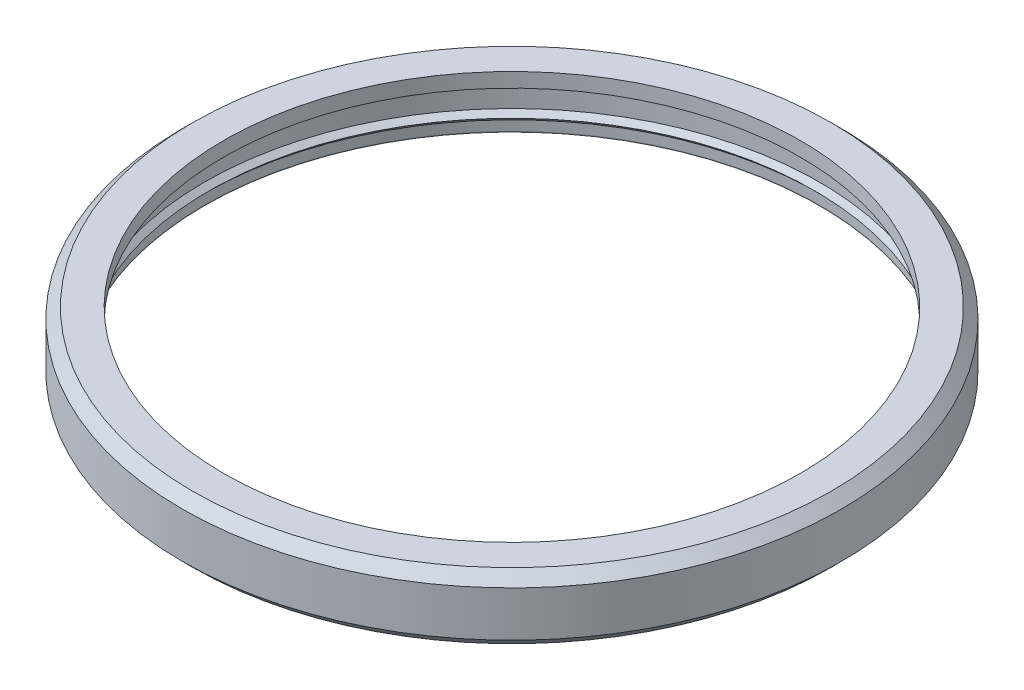
SolidWorks part; units mm, degrees
ref_plane "前视基准面" through (0, 0, 0) normal (0, 0, 1) x (1, 0, 0)
ref_plane "上视基准面" through (0, 0, 0) normal (0, 1, 0) x (1, 0, 0)
ref_plane "右视基准面" through (0, 0, 0) normal (1, 0, 0) x (0, 0, -1)
sketch "草图1" plane through (0, 0, 0) normal (0, 1, 0) x (1, 0, 0)
  circle A0 centre (0, 0) radius 32
  dimension "D1" = 64
extrude "凸台-拉伸1" add sketch "草图1" along normal blind 2.4
sketch "草图2" plane through (0, 0, 0) normal (0, 0, 1) x (1, 0, 0)
  line L0 (-32, 0) -> (32, 0) construction
  line L1 (31, -5) -> (24.3461, -5) construction
  line L6 (28.8, 0) -> (32, 0)
  line L7 (31, -5) -> (29.85, -5)
  line L12 (32, 0) -> (32, -5)
  line L13 (32, -5) -> (31, -5)
  line L18 (29.85, -4.95) -> (29.8282, -3.9575)
  line L19 (29.8282, -3.9575) -> (29.3707, -3.5)
  line L20 (29.3707, -3.5) -> (29.85, -3.0207)
  line L21 (29.85, -3.0207) -> (29.85, -1)
  line L22 (29.2472, -0.05) -> (31.95, -0.05) construction
  line L23 (31.95, -0.05) -> (31.95, -4.95) construction
  line L24 (31, -4.95) -> (29.85, -4.95) construction
  line L25 (31.95, -4.95) -> (31, -4.95) construction
  line L26 (29.85, -4.95) -> (29.85, -5)
  line L27 (31, -5) -> (29.8011, -5) construction
  line L28 (29.8, -3) -> (29.8, -1) construction
  line L29 (29.3, -3.5) -> (29.8, -3) construction
  line L30 (29.7787, -3.9787) -> (29.3, -3.5) construction
  line L31 (29.8011, -5) -> (29.7787, -3.9787) construction
  line L32 (29.8, -3) -> (29.8, -1) construction
  line L33 (29.8, -4) -> (29.3, -3.5) construction
  line L34 (29.3, -3.5) -> (29.8, -3) construction
  line L36 (0, -25) -> (0, 16.7887) construction
  arc A3 (29.85, -1) -> (29.2472, -0.05) centre (28.8, -1) ccw construction
  arc A4 (29.85, -1) -> (28.8, 0) centre (28.8488, -1) ccw
  arc A6 (29.8, -1) -> (28.8, 0) centre (28.8, -1) ccw construction
  dimension "D2" = 0.05
  dimension "D3" = 0.05
  dimension "D4" = 0.05
  dimension "D1" = 0.05
revolve "旋转1" add sketch "草图2" angle 360 about L36 region at (30.8739, -2.4787, 0)
sketch "草图3" plane through (0, 2.4, 0) normal (0, 1, 0) x (1, 0, 0)
  circle A0 centre (0, 0) radius 28
  circle A1 centre (0, 0) radius 32 construction
  dimension "D1" = 4
extrude "切除-拉伸1" cut sketch "草图3" against normal blind 10
sketch "草图4" plane through (0, 2.4, 0) normal (0, 1, 0) x (1, 0, 0)
  circle A1 centre (0, 0) radius 32
  circle A2 centre (0, 0) radius 32
  dimension "D1" = 0
extrude "切除-拉伸2" cut sketch "草图4" against normal blind 1
chamfer "倒角1" distance 1 angle 45 1 edges at (32, -5, 0)
chamfer "倒角2" distance 1 angle 45 1 edges at (0, 1.4, 32)
